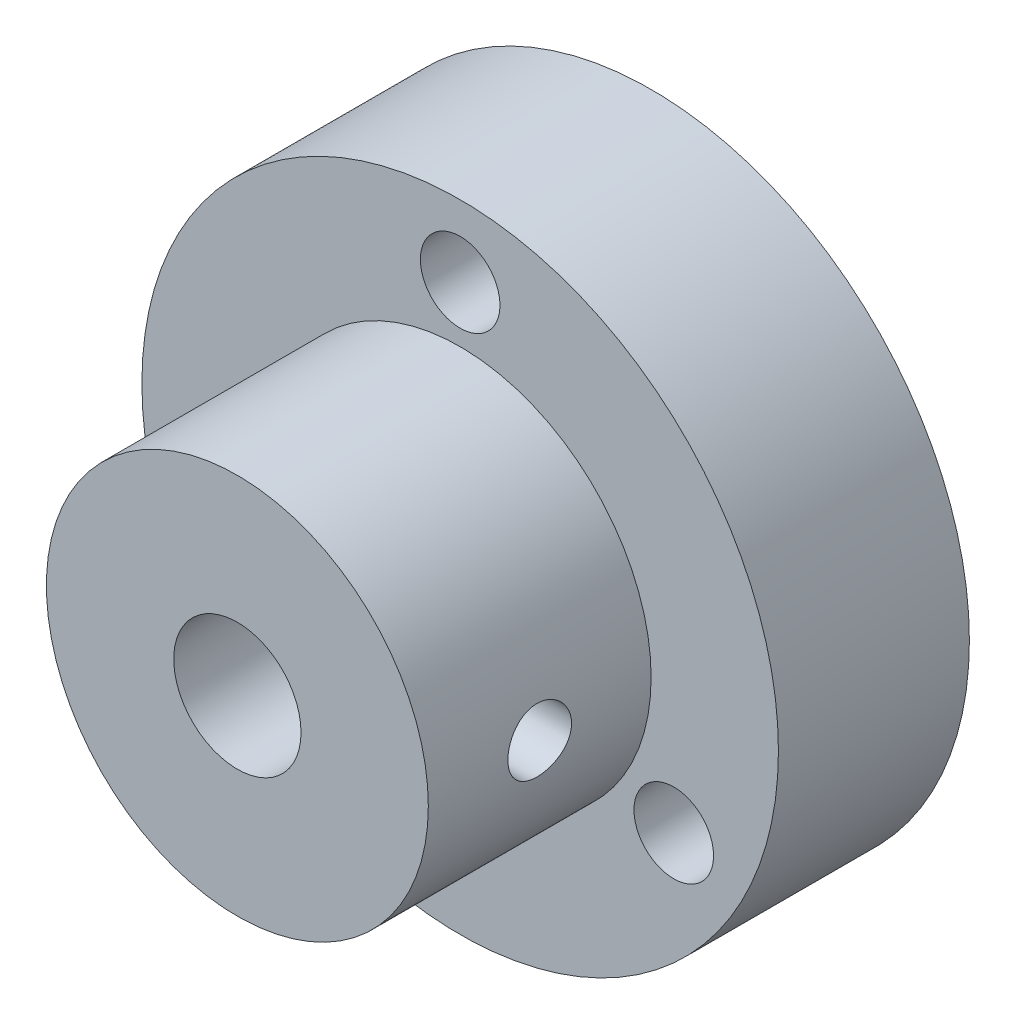
SolidWorks part; units mm, degrees
ref_plane "Front Plane" through (0, 0, 0) normal (0, 0, 1) x (1, 0, 0)
ref_plane "Top Plane" through (0, 0, 0) normal (0, 1, 0) x (1, 0, 0)
ref_plane "Right Plane" through (0, 0, 0) normal (1, 0, 0) x (0, 0, -1)
sketch "Sketch1" plane through (0, 0, 0) normal (0, 0, 1) x (1, 0, 0)
  circle A0 centre (0, 0) radius 20
  circle A1 centre (0, 0) radius 12
  circle A2 centre (0, 0) radius 4
  dimension "D1" = 40
  dimension "D2" = 24
  dimension "D3" = 8
extrude "Boss-Extrude1" add sketch "Sketch1" along normal blind 12 contours A0 A1 | A1 A2 | A2 region at (-19.4343, 0, 0) region at (-11.6606, 0, 0) region at (0, 0, 0)
extrude "Boss-Extrude2" add sketch "Sketch1<3>" along normal blind 26 contours A1 A2 | A2 region at (-11.6606, 0, 0) region at (0, 0, 0)
sketch "Sketch1<3>" plane through (0, 0, 0) normal (0, 0, 1) x (1, 0, 0) same geometry as "Sketch1"
extrude "Cut-Extrude1" cut sketch "Sketch1<4>" against normal through all both and the other way through all contours A2 region at (0, 0, 0)
sketch "Sketch1<4>" plane through (0, 0, 0) normal (0, 0, 1) x (1, 0, 0) same geometry as "Sketch1"
sketch "Sketch2" plane through (0, 0, 0) normal (1, 0, 0) x (0, 0, -1)
  line L0 (-26, 12) -> (-26, -12) construction
  circle A0 centre (-19, 0) radius 2
  dimension "D1" = 4
  dimension "D2" = 7
extrude "Cut-Extrude2" cut sketch "Sketch2" against normal through all both and the other way through all
sketch "Sketch3" plane through (0, 0, 12) normal (0, 0, 1) x (1, 0, 0)
  line L0 (0, 0) -> (26.5189, -15.3107) construction
  line L1 (0, 0) -> (0, 29.8021) construction
  circle A0 centre (0, 0) radius 15.5 construction
  circle A1 centre (0, 15.5) radius 2.5
  dimension "D1" = 31
  dimension "D3" = 5
  dimension "D2" = 120
extrude "Cut-Extrude3" cut sketch "Sketch3" against normal blind 26 and the other way through all
pattern_circular "CirPattern1" count 3 over 360 about axis through (0, 0, 26) along (0, 0, -1) of "Cut-Extrude3"
